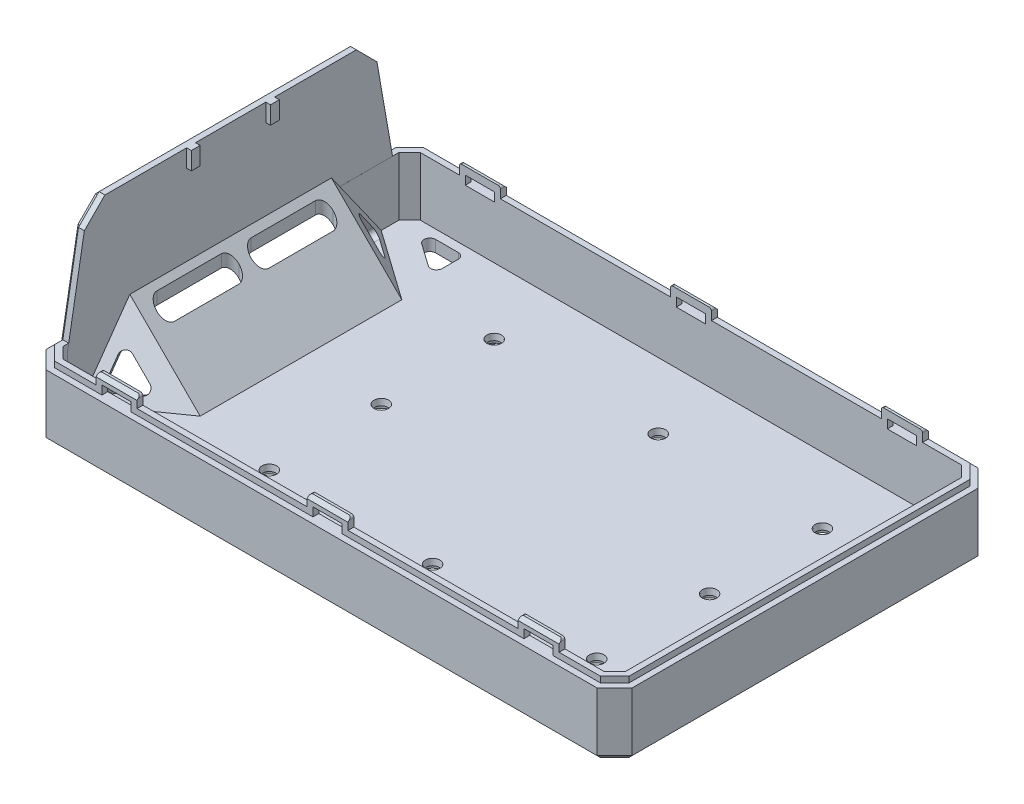
SolidWorks part; units mm, degrees
ref_plane "前视基准面" through (0, 0, 0) normal (0, 0, 1) x (1, 0, 0)
ref_plane "上视基准面" through (0, 0, 0) normal (0, 1, 0) x (1, 0, 0)
ref_plane "右视基准面" through (0, 0, 0) normal (1, 0, 0) x (0, 0, -1)
sketch "草图1" plane through (0, 0, 0) normal (0, 1, 0) x (1, 0, 0)
  line L1 (-50, 32.5) -> (50, 32.5)
  line L2 (-50, 32.5) -> (-50, -32.5)
  line L3 (-50, -32.5) -> (50, -32.5)
  line L4 (50, 32.5) -> (50, -32.5)
  line L5 (-50, 32.5) -> (50, -32.5) construction
  line L6 (-50, -32.5) -> (50, 32.5) construction
  point P0 (0, 0)
  dimension "D1" = 100
  dimension "D2" = 65
extrude "凸台-拉伸1" add sketch "草图1" along normal blind 2
sketch "草图2" plane through (-50, 0, 0) normal (-1, 0, 0) x (0, 0, 1)
  line L0 (21.45, 21.8) -> (24.96, 18.2745)
  line L1 (-24.9603, 18.2745) -> (-21.45, 21.8)
  line L2 (-32.5, 2) -> (-32.5, 0) construction
  line L8 (27.8018, 2) -> (24.96, 18.2745)
  line L9 (21.45, 21.8) -> (-21.45, 21.8)
  line L10 (-24.9603, 18.2745) -> (-27.7957, 2)
  line L11 (-32.5, 2) -> (32.5, 2) construction
  line L12 (27.8018, 2) -> (-27.7957, 2)
  line L13 (32.5, 2) -> (32.5, 0) construction
  dimension "D1" = 4.7043
  dimension "D2" = 4.6982
  dimension "D3" = 7.5397
  dimension "D4" = 7.54
  dimension "D5" = 11.05
  dimension "D6" = 11.05
  dimension "D7" = 19.8
  dimension "D8" = 16.2745
extrude "凸台-拉伸2" add sketch "草图2" against normal blind 2
ref_plane "基准面1" through (0, 0, 0) normal (0, 0, 1) x (1, 0, 0)
sketch "草图7" plane through (0, 0, 0) normal (0, 0, 1) x (1, 0, 0)
  line L0 (-49.0528, 11.84) -> (-38.4862, 1.2734)
chamfer "倒角12" distance 3 angle 45 4 edges at (50, 1, -32.5) (-50, 1, -32.5) (50, 1, 32.5) (-50, 1, 32.5)
sketch "草图22" plane through (-50, 0, 0) normal (-1, 0, 0) x (0, 0, 1)
  line L30 (26.8041, 2) -> (29.7, 2)
  line L31 (29.7, 2) -> (29.7, 34.2)
  line L32 (29.7, 34.2) -> (-29.7, 34.2)
  line L33 (-29.7, 34.2) -> (-29.7, 2)
  line L34 (-29.7, 2) -> (-26.7778, 2)
  line L35 (-26.7778, 2) -> (-24.0292, 17.782)
  line L36 (-24.0292, 17.782) -> (-21.0345, 20.7896)
  line L37 (-21.0345, 20.7896) -> (21.0345, 20.7896)
  line L38 (21.0345, 20.7896) -> (24.0291, 17.7818)
  line L39 (24.0291, 17.7818) -> (26.8041, 2)
extrude "切除-拉伸15" cut sketch "草图22" against normal blind 1
sketch "草图23" plane through (-48, 0, 0) normal (1, 0, 0) x (0, 0, -1)
  line L0 (-21.45, 21.8) -> (21.45, 21.8) construction
  line L1 (-7.5, 21.8) -> (-6, 21.8)
  line L2 (-7.5, 21.8) -> (-7.5, 18.7776)
  line L3 (-7.5, 18.7776) -> (-6, 18.7776)
  line L4 (-6, 21.8) -> (-6, 18.7776)
  line L5 (-21.45, 21.8) -> (21.45, 21.8) construction
  line L6 (7.5, 21.8) -> (6, 21.8)
  line L7 (7.5, 21.8) -> (7.5, 18.7776)
  line L8 (7.5, 18.7776) -> (6, 18.7776)
  line L9 (6, 21.8) -> (6, 18.7776)
extrude "凸台-拉伸7" add sketch "草图23" along normal blind 0.8
sketch "草图25" plane through (0, 2, 0) normal (0, 1, 0) x (1, 0, 0)
  line L16 (-46.172, 30.5307) -> (-48.0004, 28.7023)
  line L17 (46.1712, 30.5307) -> (-46.172, 30.5307)
  line L18 (47.9996, 28.7023) -> (46.1712, 30.5307)
  line L19 (47.9996, -28.6408) -> (47.9996, 28.7023)
  line L20 (46.1712, -30.4693) -> (47.9996, -28.6408)
  line L21 (-46.172, -30.4693) -> (46.1712, -30.4693)
  line L22 (-48.0004, -28.6408) -> (-46.172, -30.4693)
  line L24 (-46.5862, 31.5307) -> (-49.0004, 29.1165)
  line L25 (46.5854, 31.5307) -> (-46.5862, 31.5307)
  line L26 (48.9996, 29.1165) -> (46.5854, 31.5307)
  line L27 (48.9996, -29.055) -> (48.9996, 29.1165)
  line L28 (46.5854, -31.4693) -> (48.9996, -29.055)
  line L29 (-46.5862, -31.4693) -> (46.5854, -31.4693)
  line L30 (-49.0004, -29.055) -> (-46.5862, -31.4693)
  line L31 (-49.0004, -29.055) -> (-49.0004, 29.1165) construction
  line L32 (-48.0004, -28.6408) -> (-48.0004, 28.7023) construction
  line L33 (-49.0004, -29.055) -> (-49, -26.8041)
  line L34 (-49, -26.8041) -> (-49, -27.8018) construction
  line L35 (-49, -26.8041) -> (-48, -26.8041)
  line L36 (-48, -26.8041) -> (-48.0004, -28.6408)
  line L37 (-48.0004, 28.7023) -> (-47.9996, 26.7778)
  line L38 (-47.9996, 26.7778) -> (-49, 26.7778)
  line L40 (-49, 26.7778) -> (-49.0004, 29.1165)
  line L41 (-48, 27.7957) -> (-48, -27.8018) construction
  line L42 (-49, 27.7957) -> (-49, 26.7778) construction
  dimension "D1" = 1
extrude "凸台-拉伸8" add sketch "草图25" along normal blind 1
sketch "草图26" plane through (0, 0, 30.4693) normal (0, 0, -1) x (-1, 0, 0)
  line L0 (-46.1712, 2) -> (46.172, 2) construction
  line L1 (-39.5, 2) -> (-32.5, 2)
  line L2 (-39.5, 2) -> (-39.5, 4.8)
  line L3 (-39.5, 4.8) -> (-32.5, 4.8)
  line L4 (-32.5, 2) -> (-32.5, 4.8)
  line L5 (-50, 2) -> (-50, 0) construction
  line L6 (-3.5, 2) -> (3.5, 2)
  line L7 (-3.5, 2) -> (-3.5, 4.8)
  line L8 (-3.5, 4.8) -> (3.5, 4.8)
  line L9 (3.5, 2) -> (3.5, 4.8)
  line L10 (32.5, 2) -> (39.5, 2)
  line L11 (32.5, 2) -> (32.5, 4.8)
  line L12 (32.5, 4.8) -> (39.5, 4.8)
  line L13 (39.5, 2) -> (39.5, 4.8)
  dimension "D1" = 10.5
  dimension "D2" = 7
  dimension "D3" = 2.8
  dimension "D4" = 29
  dimension "D5" = 29
extrude "凸台-拉伸9" add sketch "草图26" against normal blind 1
sketch "草图27" plane through (0, 0, -30.5307) normal (0, 0, 1) x (1, 0, 0)
  line L4 (-39.5, 2) -> (-32.5, 2)
  line L5 (-39.5, 4.8) -> (-39.5, 2)
  line L6 (-32.5, 4.8) -> (-39.5, 4.8)
  line L7 (-32.5, 2) -> (-32.5, 4.8)
  line L8 (-39.5, 2) -> (-32.5, 2)
  line L9 (-39.5, 4.8) -> (-39.5, 2)
  line L10 (-32.5, 4.8) -> (-39.5, 4.8)
  line L11 (-32.5, 2) -> (-32.5, 4.8)
  line L12 (-3.5, 2) -> (3.5, 2)
  line L13 (-3.5, 4.8) -> (-3.5, 2)
  line L14 (3.5, 4.8) -> (-3.5, 4.8)
  line L15 (3.5, 2) -> (3.5, 4.8)
  line L16 (-3.5, 2) -> (3.5, 2)
  line L17 (-3.5, 4.8) -> (-3.5, 2)
  line L18 (3.5, 4.8) -> (-3.5, 4.8)
  line L19 (3.5, 2) -> (3.5, 4.8)
  line L20 (32.5, 2) -> (39.5, 2)
  line L21 (32.5, 4.8) -> (32.5, 2)
  line L22 (39.5, 4.8) -> (32.5, 4.8)
  line L23 (39.5, 2) -> (39.5, 4.8)
  line L24 (32.5, 2) -> (39.5, 2)
  line L25 (32.5, 4.8) -> (32.5, 2)
  line L26 (39.5, 4.8) -> (32.5, 4.8)
  line L27 (39.5, 2) -> (39.5, 4.8)
  dimension "D1" = 0
  dimension "D2" = 0
  dimension "D3" = 0
extrude "凸台-拉伸10" add sketch "草图27" against normal blind 1
sketch "草图28" plane through (0, 0, -31.5307) normal (0, 0, -1) x (-1, 0, 0)
  line L0 (-46.5854, 2) -> (46.5862, 2) construction
  line L1 (-38.5033, 2) -> (-33.5033, 2)
  line L2 (-38.5033, 2) -> (-38.5033, 3.5)
  line L3 (-38.5033, 3.5) -> (-33.5033, 3.5)
  line L4 (-33.5033, 2) -> (-33.5033, 3.5)
  line L6 (-2.5033, 2) -> (2.4967, 2)
  line L7 (-2.5033, 2) -> (-2.5033, 3.5)
  line L8 (-2.5033, 3.5) -> (2.4967, 3.5)
  line L9 (2.4967, 2) -> (2.4967, 3.5)
  line L10 (33.5, 2) -> (38.5, 2)
  line L11 (33.5, 2) -> (33.5, 3.5)
  line L12 (33.5, 3.5) -> (38.5, 3.5)
  line L13 (38.5, 2) -> (38.5, 3.5)
  dimension "D1" = 11.5
  dimension "D2" = 5
  dimension "D3" = 1.5
  dimension "D4" = 31.0033
  dimension "D5" = 31
extrude "切除-拉伸16" cut sketch "草图28" against normal blind 0.5
chamfer "倒角14" distance 0.6 angle 45 6 edges at (-36, 4.8, -31.5307) (-36, 4.8, 31.4693) (0, 4.8, 31.4693) (0, 4.8, -31.5307) (36, 4.8, -31.5307) (36, 4.8, 31.4693)
fillet "圆角6" radius 0.4 12 edges at (39.5, 4.8, 30.6693) (32.5, 4.8, 30.6693) (3.5, 4.8, 30.6693) (-3.5, 4.8, 30.6693) (-32.5, 4.8, 30.6693) (-39.5, 4.8, 30.6693) (-39.5, 4.8, -30.7307) (-32.5, 4.8, -30.7307) (-3.5, 4.8, -30.7307) (3.5, 4.8, -30.7307) (32.5, 4.8, -30.7307) (39.5, 4.8, -30.7307)
sketch "草图31" plane through (0, 0, 0) normal (0, -1, 0) x (1, 0, 0)
  line L8 (-47, -32.5) -> (47, -32.5)
  line L9 (47, -32.5) -> (50, -29.5)
  line L10 (50, -29.5) -> (50, 29.5)
  line L11 (50, 29.5) -> (47, 32.5)
  line L12 (47, 32.5) -> (-47, 32.5)
  line L13 (-47, 32.5) -> (-50, 29.5)
  line L14 (-50, 29.5) -> (-50, -29.5)
  line L15 (-50, -29.5) -> (-47, -32.5)
  line L16 (-47, -32.5) -> (47, -32.5)
  line L17 (47, -32.5) -> (50, -29.5)
  line L18 (50, -29.5) -> (50, 29.5)
  line L19 (50, 29.5) -> (47, 32.5)
  line L20 (47, 32.5) -> (-47, 32.5)
  line L21 (-47, 32.5) -> (-50, 29.5)
  line L22 (-50, 29.5) -> (-50, -29.5)
  line L23 (-50, -29.5) -> (-47, -32.5)
  dimension "D1" = 0
extrude "凸台-拉伸11" add sketch "草图31" along normal blind 9
sketch "草图32" plane through (0, 2, 0) normal (0, 1, 0) x (1, 0, 0)
  line L12 (-48.0004, 28.7023) -> (-47.9996, 26.7778)
  line L13 (-47.9996, 26.7778) -> (-48, 26.7778)
  line L14 (-48, 26.7778) -> (-48, -27.8018)
  line L15 (-48, -27.8018) -> (-48.0002, -27.8018)
  line L16 (-48.0002, -27.8018) -> (-48.0004, -28.6408)
  line L17 (-48.0004, -28.6408) -> (-46.172, -30.4693)
  line L18 (-46.172, -30.4693) -> (46.1712, -30.4693)
  line L23 (-46.172, 30.5307) -> (-48.0004, 28.7023)
  line L24 (-48.0004, 28.7023) -> (-47.9996, 26.7778)
  line L25 (-47.9996, 26.7778) -> (-48, 26.7778)
  line L26 (-48, 26.7778) -> (-48, -27.8018)
  line L27 (-48, -27.8018) -> (-48.0002, -27.8018)
  line L28 (-48.0002, -27.8018) -> (-48.0004, -28.6408)
  line L29 (-48.0004, -28.6408) -> (-46.172, -30.4693)
  line L30 (-46.172, -30.4693) -> (46.1712, -30.4693)
  line L35 (-46.172, 30.5307) -> (-48.0004, 28.7023)
  line L160 (46.1712, -30.4693) -> (47.9996, -28.6408)
  line L180 (46.1712, -30.4693) -> (47.9996, -28.6408)
  line L182 (47.9996, -28.6408) -> (47.9996, 28.7023)
  line L184 (47.9996, -28.6408) -> (47.9996, 28.7023)
  line L186 (47.9996, 28.7023) -> (46.1712, 30.5307)
  line L188 (47.9996, 28.7023) -> (46.1712, 30.5307)
  line L190 (46.1712, 30.5307) -> (-46.172, 30.5307)
  line L192 (46.1712, 30.5307) -> (-46.172, 30.5307)
  dimension "D1" = 0
extrude "切除-拉伸18" cut sketch "草图32" against normal blind 9
sketch "草图33" plane through (0, -9, 0) normal (0, -1, 0) x (1, 0, 0)
  line L0 (-47, -32.5) -> (47, -32.5) construction
  line L2 (50, -29.5) -> (50, 29.5) construction
  circle A0 centre (5.7043, -19.25) radius 2
  circle A1 centre (5.7043, 19.25) radius 2
  circle A2 centre (-22.1454, 19.25) radius 2
  circle A3 centre (-22.2957, 0) radius 2
  circle A4 centre (-22.2957, -19.25) radius 2
  circle A5 centre (33.7043, 19.25) radius 2
  circle A6 centre (33.7043, -19.25) radius 2
  circle A7 centre (33.7043, 0) radius 2
  dimension "D1" = 38.5
  dimension "D2" = 13.25
  dimension "D3" = 44.2957
  dimension "D4" = 19.25
extrude "切除-拉伸19" cut sketch "草图33" against normal blind 1
sketch "草图34" plane through (0, -8, 0) normal (0, -1, 0) x (1, 0, 0)
  circle A0 centre (5.7043, -19.25) radius 1.1
  circle A1 centre (5.7043, 19.25) radius 1.1
  circle A2 centre (5.7043, -19.25) radius 2 construction
  circle A3 centre (5.7043, 19.25) radius 2 construction
  circle A4 centre (-22.1454, 19.25) radius 1.1
  circle A5 centre (33.7043, 19.25) radius 1.1
  circle A6 centre (-22.2957, 0) radius 1.1
  circle A7 centre (-22.2957, -19.25) radius 1.1
  circle A8 centre (33.7043, 0) radius 1.1
  circle A9 centre (33.7043, -19.25) radius 1.1
  circle A10 centre (-22.1454, 19.25) radius 2 construction
  circle A11 centre (-22.2957, 0) radius 2 construction
  circle A12 centre (-22.2957, -19.25) radius 2 construction
  circle A13 centre (33.7043, 19.25) radius 2 construction
  circle A14 centre (33.7043, 0) radius 2 construction
  circle A15 centre (33.7043, -19.25) radius 2 construction
  dimension "D1" = 2.2
extrude "切除-拉伸20" cut sketch "草图34" against normal blind 1 draft 8 draft outward yes
sketch "草图35" plane through (0, 0, 0) normal (0, 0, 1) x (1, 0, 0)
  line L5 (-49, 6) -> (-35, -8)
rib "筋4" sketch "草图35" sketch "草图35" thickness 54 extrusion direction parallel to sketch draft on no parameters "D1"=54
sketch "草图36" plane through (0, 0, 0) normal (0, 0, 1) x (1, 0, 0)
  line L0 (-51.8363, 6.7149) -> (-34.7338, -10.3875)
  line L1 (-34.7338, -10.3875) -> (-51.8363, -10.3875)
  line L2 (-51.8363, -10.3875) -> (-51.8363, 6.7149)
  line L3 (-48, 5) -> (-36, -7) construction
  dimension "D1" = 1.5
extrude "切除-拉伸22" cut sketch "草图36" against normal blind 26 and the other way blind 26
chamfer "倒角15" distance 9.8 angle 45 4 edges at (-43.0607, -2.0607, -26) (-43.0607, -2.0607, 26) (-42, -1, -27) (-42, -1, 27)
sketch "草图37" plane through (0, -9, 0) normal (0, -1, 0) x (1, 0, 0)
  line L0 (-47, -32.5) -> (47, -32.5) construction
  line L1 (-47, -15) -> (-44, -15)
  line L2 (-47, -15) -> (-47, -1)
  line L3 (-47, -1) -> (-44, -1)
  line L4 (-44, -15) -> (-44, -1)
  line L5 (-47.1, 1) -> (-44.1, 1)
  line L6 (-47.1, 1) -> (-47.1, 15)
  line L7 (-47.1, 15) -> (-44.1, 15)
  line L8 (-44.1, 1) -> (-44.1, 15)
  line L9 (47, 32.5) -> (-47, 32.5) construction
  line L10 (-50, -26) -> (-50, -29.5) construction
  dimension "D1" = 17.5
  dimension "D2" = 17.5
  dimension "D3" = 14
  dimension "D4" = 3
  dimension "D5" = 3
extrude "切除-拉伸25" cut sketch "草图37" against normal blind 20
fillet "圆角7" radius 1.5 8 edges at (-44.1, 0.0393, 15) (-44.1, 0.0393, 1) (-47.1, 3.0393, 15) (-47.1, 3.0393, 1) (-44, -0.0607, -15) (-44, -0.0607, -1) (-47, 2.9393, -1) (-47, 2.9393, -15)
sketch "草图38" plane through (-5.5528, -5.5528, -7.8528) normal (-0.5, -0.5, -0.7071) x (-0.866, 0.2887, 0.4082)
  line L8 (41.7616, -15.805) -> (48.3232, -18.1249)
  line L9 (48.3232, -18.1249) -> (48.3232, -11.1652)
  line L10 (48.3232, -11.1652) -> (41.7616, -15.805)
  line L11 (41.7616, -15.805) -> (48.3232, -18.1249)
  line L12 (48.3232, -18.1249) -> (48.3232, -11.1652)
  line L13 (48.3232, -11.1652) -> (41.7616, -15.805)
  dimension "D1" = 3
extrude "切除-拉伸26" cut sketch "草图38" against normal blind 2
sketch "草图39" plane through (-5.5528, -5.5528, 7.8528) normal (-0.5, -0.5, 0.7071) x (0.866, -0.2887, 0.4082)
  line L8 (-48.3232, -18.1249) -> (-41.7616, -15.805)
  line L9 (-41.7616, -15.805) -> (-48.3232, -11.1652)
  line L10 (-48.3232, -11.1652) -> (-48.3232, -18.1249)
  line L11 (-48.3232, -18.1249) -> (-41.7616, -15.805)
  line L12 (-41.7616, -15.805) -> (-48.3232, -11.1652)
  line L13 (-48.3232, -11.1652) -> (-48.3232, -18.1249)
  dimension "D1" = 3
extrude "切除-拉伸27" cut sketch "草图39" against normal blind 2
fillet "圆角8" radius 1 6 edges at (-41.2775, -5.96, 18.9463) (-46.96, -5.96, 22.9645) (-46.96, -0.2775, 18.9463) (-41.2775, -5.96, -18.9463) (-46.96, -5.96, -22.9645) (-46.96, -0.2775, -18.9463)
chamfer "倒角16" distance 1 angle 45 11 edges at (-43.051, -9, -21.1) (-43.051, -9, 21.1) (-50, -9, -27.75) (-48.5, -9, -31) (0, -9, -32.5) (48.5, -9, -31) (50, -9, 0) (48.5, -9, 31) (-50, -9, 27.75) (0, -9, 32.5) (-48.5, -9, 31) first distance on face at (-45.572, -4.572, -19.7516) first distance on face at (-45.572, -4.572, 19.7516) first distance on face at (-50, 2.5587, 0.0016) first distance on face at (-48.5, -3.5, -31) first distance on face at (0, -3.5, -32.5) first distance on face at (48.5, -3.5, -31) first distance on face at (50, -3.5, 0) first distance on face at (48.5, -3.5, 31) first distance on face at (0, -3.5, 32.5) first distance on face at (-48.5, -3.5, 31)
sketch "草图40" plane through (0, -9, 0) normal (0, -1, 0) x (1, 0, 0)
  line L0 (50, 29.5) -> (50, -29.5) construction
  line L1 (47, -32.5) -> (-47, -32.5) construction
  line L2 (-47, 32.5) -> (47, 32.5) construction
  line L3 (-50, -29.5) -> (-50, -25.3066) construction
  circle A0 centre (41.5, -22.5) radius 6
  circle A1 centre (-30.5, -22.5) radius 6
  circle A2 centre (41.5, 22.5) radius 6
  circle A3 centre (-30.5, 22.5) radius 6
  dimension "D1" = 12
  dimension "D2" = 8.5
  dimension "D3" = 10
  dimension "D4" = 10
  dimension "D5" = 19.5
extrude "凸台-拉伸12" add sketch "草图40" along normal blind 1
sketch "草图41" plane through (0, -10, 0) normal (0, -1, 0) x (1, 0, 0)
  circle A0 centre (41.5, -22.5) radius 5
  circle A1 centre (41.5, 22.5) radius 5
  circle A2 centre (-30.5, 22.5) radius 5
  circle A3 centre (-30.5, -22.5) radius 5
  dimension "D1" = 10
extrude "切除-拉伸28" cut sketch "草图41" against normal blind 0.5
sketch "草图42" plane through (0, -9, 0) normal (0, -1, 0) x (1, 0, 0)
  line L18 (-45.1611, -29) -> (-37.164, -23.3452)
  line L19 (-37.164, -23.3452) -> (-37.164, -29)
  line L20 (-37.164, -29) -> (-45.1611, -29)
  line L21 (-45.1611, 29) -> (-37.8546, 23.8336)
  line L22 (-37.8546, 23.8336) -> (-37.8546, 29)
  line L23 (-37.8546, 29) -> (-45.1611, 29)
extrude "切除-拉伸29" cut sketch "草图42" against normal blind 2
fillet "圆角9" radius 1 6 edges at (-37.8546, -8, 23.8336) (-37.8546, -8, 29) (-45.1611, -8, 29) (-37.164, -8, -23.3452) (-37.164, -8, -29) (-45.1611, -8, -29)
sketch "草图43" plane through (0, 0, 30.4693) normal (0, 0, -1) x (-1, 0, 0)
  line L0 (39.5, 3) -> (39.5, 4.4) construction
  line L2 (-39.5, 3) -> (-39.5, 0.5)
  line L3 (-39.5, 0.5) -> (-32.5, 0.5)
  line L4 (-32.5, 3) -> (-32.5, 0.5)
  line L6 (-3.5, 3) -> (-3.5, 0.5)
  line L7 (-3.5, 0.5) -> (3.5, 0.5)
  line L8 (3.5, 3) -> (3.5, 0.5)
  line L14 (32.5, 3) -> (32.5, 0.5)
  line L15 (32.5, 0.5) -> (39.5, 0.5)
  line L16 (39.5, 3) -> (39.5, 0.5)
  line L17 (39.1, 4.8) -> (32.9, 4.8) construction
  line L18 (32.5, 4.4) -> (32.5, 3) construction
  line L19 (3.5, 3) -> (3.5, 4.4) construction
  line L20 (3.1, 4.8) -> (-3.1, 4.8) construction
  line L21 (-3.5, 4.4) -> (-3.5, 3) construction
  line L22 (-32.5, 3) -> (-32.5, 4.4) construction
  line L23 (-32.9, 4.8) -> (-39.1, 4.8) construction
  line L24 (-39.5, 4.4) -> (-39.5, 3) construction
  line L25 (39.5, 3) -> (39.5, 4.4)
  line L26 (39.1, 4.8) -> (32.9, 4.8)
  line L27 (32.5, 4.4) -> (32.5, 3)
  line L28 (3.5, 3) -> (3.5, 4.4)
  line L29 (3.1, 4.8) -> (-3.1, 4.8)
  line L30 (-3.5, 4.4) -> (-3.5, 3)
  line L31 (-32.5, 3) -> (-32.5, 4.4)
  line L32 (-32.9, 4.8) -> (-39.1, 4.8)
  line L33 (-39.5, 4.4) -> (-39.5, 3)
  arc A0 (39.5, 4.4) -> (39.1, 4.8) centre (39.1, 4.4) ccw construction
  arc A1 (32.9, 4.8) -> (32.5, 4.4) centre (32.9, 4.4) ccw construction
  arc A2 (3.5, 4.4) -> (3.1, 4.8) centre (3.1, 4.4) ccw construction
  arc A3 (-3.1, 4.8) -> (-3.5, 4.4) centre (-3.1, 4.4) ccw construction
  arc A4 (-32.5, 4.4) -> (-32.9, 4.8) centre (-32.9, 4.4) ccw construction
  arc A5 (-39.1, 4.8) -> (-39.5, 4.4) centre (-39.1, 4.4) ccw construction
  arc A6 (39.5, 4.4) -> (39.1, 4.8) centre (39.1, 4.4) ccw
  arc A7 (32.9, 4.8) -> (32.5, 4.4) centre (32.9, 4.4) ccw
  arc A8 (3.5, 4.4) -> (3.1, 4.8) centre (3.1, 4.4) ccw
  arc A9 (-3.1, 4.8) -> (-3.5, 4.4) centre (-3.1, 4.4) ccw
  arc A10 (-32.5, 4.4) -> (-32.9, 4.8) centre (-32.9, 4.4) ccw
  arc A11 (-39.1, 4.8) -> (-39.5, 4.4) centre (-39.1, 4.4) ccw
  dimension "D1" = 2.5
sketch "草图44" plane through (0, 0, -31.0307) normal (0, 0, -1) x (-1, 0, 0)
  line L0 (33.5, 3.5) -> (33.5, 2) construction
  line L1 (33.5, 2) -> (38.5, 2) construction
  line L2 (38.5, 2) -> (38.5, 3.5) construction
  line L3 (38.5, 3.5) -> (33.5, 3.5) construction
  line L4 (-2.5033, 3.5) -> (-2.5033, 2) construction
  line L5 (-2.5033, 2) -> (2.4967, 2) construction
  line L6 (2.4967, 2) -> (2.4967, 3.5) construction
  line L7 (2.4967, 3.5) -> (-2.5033, 3.5) construction
  line L8 (-38.5033, 3.5) -> (-38.5033, 2) construction
  line L9 (-38.5033, 2) -> (-33.5033, 2) construction
  line L10 (-33.5033, 2) -> (-33.5033, 3.5) construction
  line L11 (-33.5033, 3.5) -> (-38.5033, 3.5) construction
  line L12 (33.5, 3.5) -> (33.5, 2)
  line L13 (33.5, 2) -> (38.5, 2)
  line L14 (38.5, 2) -> (38.5, 3.5)
  line L15 (38.5, 3.5) -> (33.5, 3.5)
  line L16 (-2.5033, 3.5) -> (-2.5033, 2)
  line L17 (-2.5033, 2) -> (2.4967, 2)
  line L18 (2.4967, 2) -> (2.4967, 3.5)
  line L19 (2.4967, 3.5) -> (-2.5033, 3.5)
  line L20 (-38.5033, 3.5) -> (-38.5033, 2)
  line L21 (-38.5033, 2) -> (-33.5033, 2)
  line L22 (-33.5033, 2) -> (-33.5033, 3.5)
  line L23 (-33.5033, 3.5) -> (-38.5033, 3.5)
extrude "切除-拉伸30" cut sketch "草图44" against normal through all
